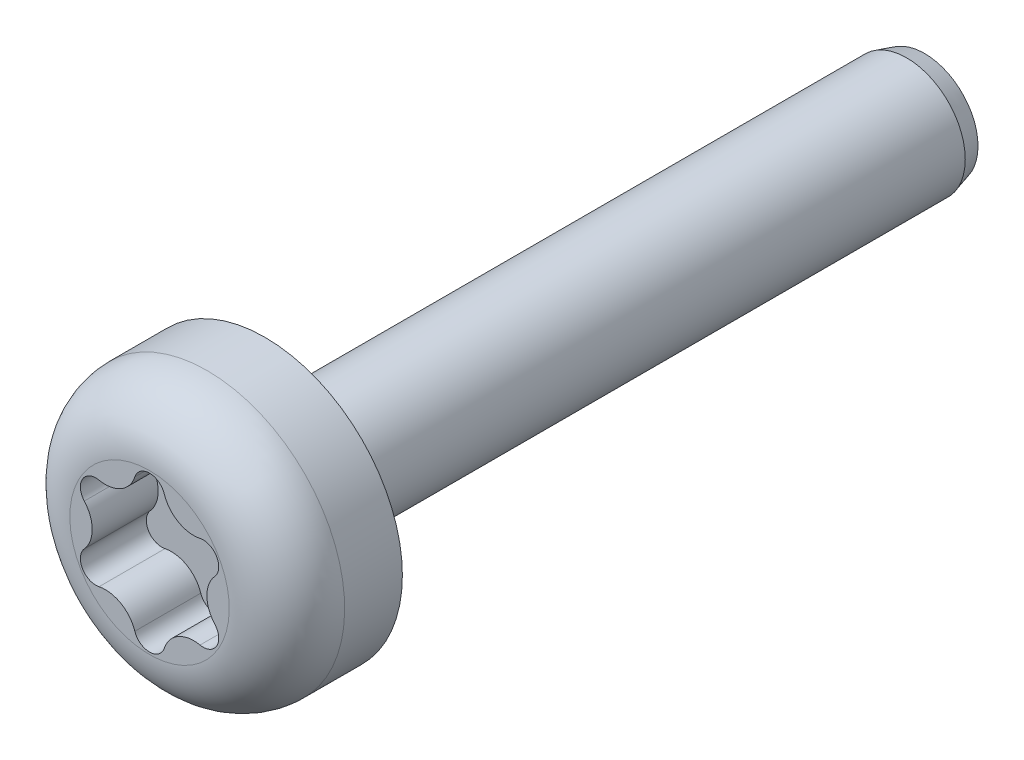
SolidWorks part; units mm, degrees
material "Alloy Steel"
ref_plane "Front" through (0, 0, 0) normal (0, 0, 1) x (1, 0, 0)
ref_plane "Top" through (0, 0, 0) normal (0, 1, 0) x (1, 0, 0)
ref_plane "Right" through (0, 0, 0) normal (1, 0, 0) x (0, 0, -1)
sketch "Sketch1" plane through (0, 0, 0) normal (0, 0, 1) x (1, 0, 0)
  circle A0 centre (0, 0) radius 2.5
  dimension "Head Dia" = 5
extrude "Extrude3" add sketch "Sketch1" along normal blind 2.1
ref_plane "Plane1" through (0, 0, 2.1) normal (0, 0, 1) x (1, 0, 0)
sketch "Sketch11" plane through (0, 0, 0) normal (1, 0, 0) x (0, 0, -1)
  line L2 (-2.1, 2.5) -> (-2.1, -2.5) construction
  line L4 (0, 2.5) -> (-2.1, 2.5) construction
  line L5 (-1.05, 2.5) -> (-1.05, 2.6)
  line L6 (-1.05, 2.6) -> (-2.2, 2.6)
  line L7 (-2.2, 2.6) -> (-2.2, 1.45)
  line L8 (-2.2, 1.45) -> (-2.1, 1.45)
  line L11 (0, 0) -> (-2.1, 0) construction
  arc A0 (-2.1, 1.45) -> (-1.05, 2.5) centre (-1.05, 1.45) cw
  dimension "D1" = 0.1
  dimension "D2" = 0.1
revolve "Cut-Revolve3" cut sketch "Sketch11" angle 360 about L11
sketch "Sketch4" plane through (0, 0, 0) normal (1, 0, 0) x (0, 0, -1)
  line L0 (0, 0) -> (12, 0)
  line L2 (12, -1.065) -> (0, -1.065) construction
  line L3 (12, 0) -> (12, 1.065)
  line L4 (12, 1.065) -> (0, 1.065)
  line L5 (0, 0) -> (-2.1, 0) construction
  line L6 (0, 1.065) -> (0, 0)
  line L7 (12, 0) -> (14.54, 0) construction
  point P7 (0, 1.065)
  dimension "D1" = 2.54
  dimension "Body Length" = 12
  dimension "Minor Dia" = 2.13
revolve "Revolve1" add sketch "Sketch4" angle 360 about L7
sketch "Sketch13" plane through (0, 0, 0) normal (1, 0, 0) x (0, 0, -1)
  line L0 (12, 0.9725) -> (10.15, 1.5)
  line L1 (12, 0) -> (12, 1.065) construction
  line L2 (10.15, 1.5) -> (12, 1.5)
  line L3 (12, 1.5) -> (12, 0.9725) construction
  line L4 (12, 0.9725) -> (12, 0)
  line L5 (0, 0) -> (12, 0) construction
  line L7 (13.27, 0) -> (13.27, 1.5)
  line L8 (13.27, 1.5) -> (12, 1.5)
  line L9 (12, 0) -> (13.27, 0)
  dimension "D1" = 3
  dimension "D3" = 1.27
  dimension "Point Dia" = 1.945
  dimension "Point Lg" = 1.85
revolve "Cut-Revolve4" cut sketch "Sketch13" angle 360 about L5
sketch "Sketch12" plane through (0, 0, 2.1) normal (0, 0, 1) x (1, 0, 0)
  line L0 (0, 0) -> (0, 1.4095) construction
  line L1 (-0.5215, 0.9033) -> (0, 0)
  line L2 (0, 0) -> (0.5215, 0.9033)
  arc A0 (-0.5215, 0.9033) -> (-0.2678, 1.2156) centre (-0.8034, 1.3916) ccw
  arc A1 (-0.2678, 1.2156) -> (0.2678, 1.2156) centre (0, 1.1276) cw
  arc A2 (0.2678, 1.2156) -> (0.5215, 0.9033) centre (0.8034, 1.3916) ccw
  circle A5 centre (0, 0) radius 1.4095 construction
  dimension "D1" = 60
  dimension "M" = 2.819
  dimension "D2" = 0.2819
  dimension "D3" = 0.5638
ref_axis "Axis1" through (0, 0, 2.1) along (0, 0, -1)
extrude "Cut-Extrude1" cut sketch "Sketch12" against normal blind 1.2
pattern_circular "CirPattern1" count 6 every 60 about axis through (0, 0, 2.1) along (0, 0, -1) of "Cut-Extrude1"
equation "\"D1@Cut-Extrude1\"=\"Head Ht@Extrude3\"*2/3.5"
equation "\"D2@Sketch12\" = \"M@Sketch12\"*.1"
equation "\"D3@Sketch12\" = \"D2@Sketch12\"*2"
